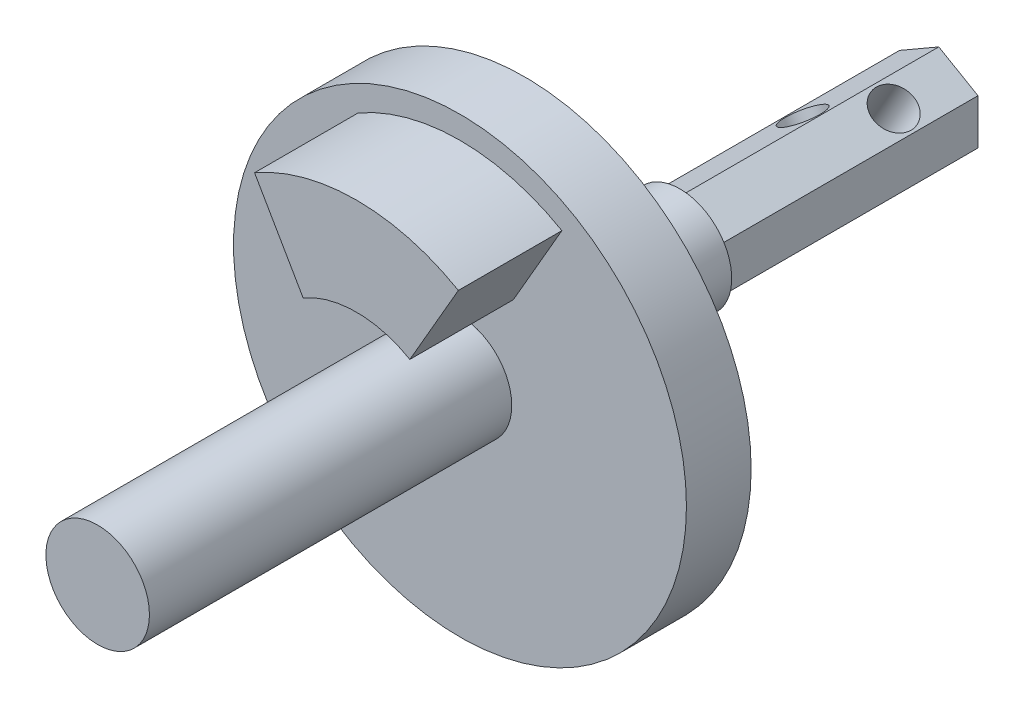
SolidWorks part; units mm, degrees
ref_plane "Front Plane" through (0, 0, 0) normal (0, 0, 1) x (1, 0, 0)
ref_plane "Top Plane" through (0, 0, 0) normal (0, 1, 0) x (1, 0, 0)
ref_plane "Right Plane" through (0, 0, 0) normal (1, 0, 0) x (0, 0, -1)
sketch "Sketch1" plane through (0, 0, 0) normal (0, 0, 1) x (1, 0, 0)
  circle A0 centre (0, 0) radius 17.5
  dimension "D1" = 35
extrude "Boss-Extrude1" add sketch "Sketch1" along normal mid plane 5
sketch "Sketch2" plane through (0, 0, 2.5) normal (0, 0, 1) x (1, 0, 0)
  line L3 (0, 0) -> (0, 11) construction
  line L4 (7.875, 13.6399) -> (4.125, 7.1447)
  line L5 (-4.125, 7.1447) -> (-7.875, 13.6399)
  arc A1 (4.125, 7.1447) -> (-4.125, 7.1447) centre (0, 0) ccw
  arc A6 (-7.875, 13.6399) -> (7.875, 13.6399) centre (0, 0) cw
  circle A7 centre (0, 0) radius 17.5 construction
  dimension "D2" = 7.5
  dimension "D3" = 1.75
  dimension "D1" = 30
extrude "Boss-Extrude2" add sketch "Sketch2" along normal blind 8
sketch "Sketch3" plane through (0, 0, 2.5) normal (0, 0, 1) x (1, 0, 0)
  circle A0 centre (0, 0) radius 4
extrude "Boss-Extrude3" add sketch "Sketch3" along normal blind 28
sketch "Sketch7" plane through (0, 0, -2.5) normal (0, 0, -1) x (-1, 0, 0)
  circle A0 centre (0, 0) radius 4
extrude "Boss-Extrude4" add sketch "Sketch7" along normal blind 12
sketch "Sketch9" plane through (0, 0, -14.5) normal (0, 0, -1) x (-1, 0, 0)
  line L11 (0, 3.5) -> (-3.0311, 1.75)
  line L12 (-3.0311, 1.75) -> (-3.0311, -1.75)
  line L13 (-3.0311, -1.75) -> (0, -3.5)
  line L14 (0, -3.5) -> (3.0311, -1.75)
  line L15 (3.0311, -1.75) -> (3.0311, 1.75)
  line L16 (3.0311, 1.75) -> (0, 3.5)
  point P5 (0, 0)
  point P6 (0, 0)
  point P8 (0, 0)
  point P11 (0, 0)
  point P13 (0, 0)
  point P15 (0, 0)
extrude "Boss-Extrude5" add sketch "Sketch9" along normal blind 20
sketch "Sketch10" plane through (-1.5155, -2.625, 0) normal (-0.5, -0.866, 0) x (0.866, -0.5, 0)
  line L0 (0, -34.5) -> (0, -29.5) construction
  line L1 (1.75, -34.5) -> (-1.75, -34.5) construction
  circle A0 centre (0, -29.5) radius 1.55
extrude "Cut-Extrude1" cut sketch "Sketch10" against normal blind 6.1
sketch "Sketch11" plane through (1.5155, -2.625, 0) normal (-0.5, 0.866, 0) x (0, 0, 1)
  line L0 (-34.5, 0) -> (-25.5, 0) construction
  line L3 (-34.5, -1.75) -> (-34.5, 1.75) construction
  circle A1 centre (-25.5, 0) radius 1.55
extrude "Cut-Extrude4" cut sketch "Sketch11" along normal blind 6.1
